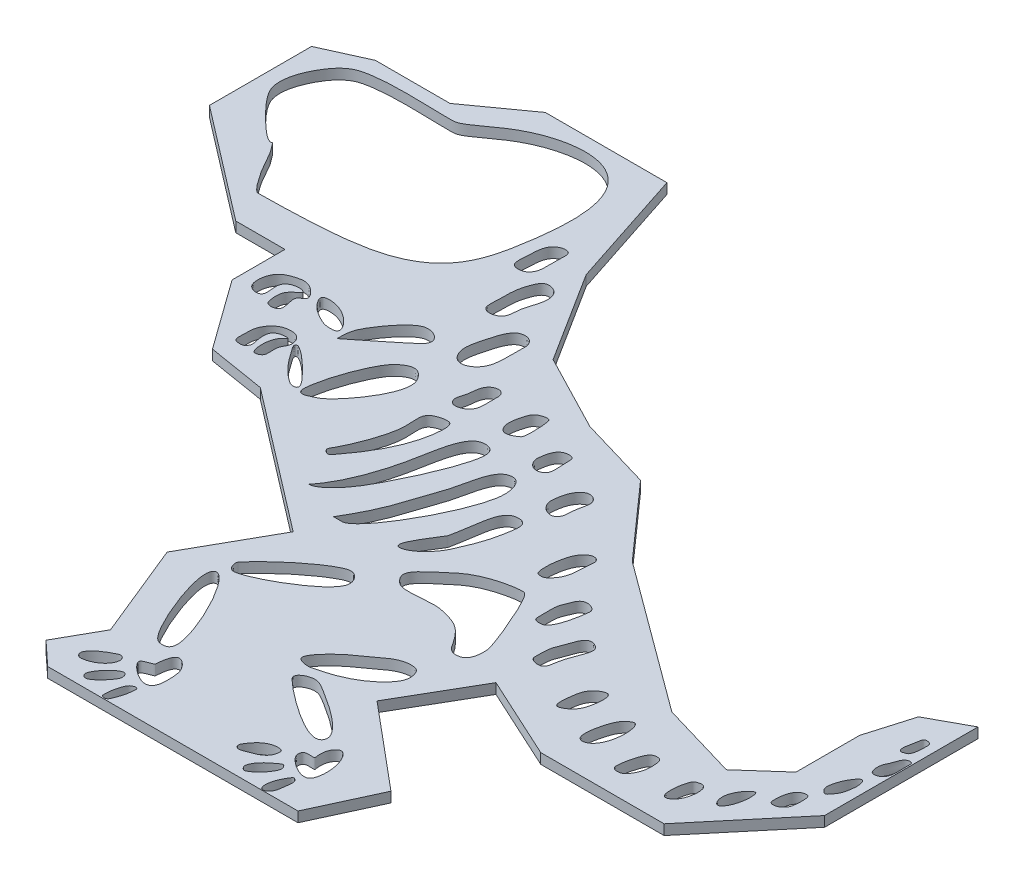
SolidWorks part; units mm, degrees
ref_plane "Front Plane" through (0, 0, 0) normal (0, 0, 1) x (1, 0, 0)
ref_plane "Top Plane" through (0, 0, 0) normal (0, 1, 0) x (1, 0, 0)
ref_plane "Right Plane" through (0, 0, 0) normal (1, 0, 0) x (0, 0, -1)
sketch "Sketch1" plane through (0, 0, 0) normal (0, 1, 0) x (1, 0, 0)
  line L0 (-169.545, -133.35) -> (169.545, 133.35) construction
  line L1 (-169.545, 133.35) -> (169.545, 133.35) construction
  line L2 (-169.545, 133.35) -> (-169.545, -133.35) construction
  line L3 (-169.545, -133.35) -> (169.545, -133.35)
  line L4 (169.545, 133.35) -> (169.545, -133.35)
  line L5 (-169.545, -133.35) -> (-174.8173, -133.35)
  line L6 (-174.8173, -133.35) -> (-174.8173, 138.6223)
  line L7 (-174.8173, 138.6223) -> (169.545, 138.6223)
  line L8 (169.545, 138.6223) -> (169.545, 133.35)
sketch "Sketch2" plane through (0, 0, 0) normal (0, 0, 1) x (1, 0, 0)
  line L0 (0, 0) -> (0, 8.058) construction
  line L1 (-169.545, 0) -> (169.545, 0) construction
sketch "Sketch3" plane through (0, 0, 0) normal (0, 1, 0) x (1, 0, 0)
  line L1 (-159.2597, 106.4446) -> (-159.6747, 106.0436)
  line L2 (-159.2597, 106.4446) -> (-159.6747, 106.0436)
  line L3 (-18.6637, -31.5909) -> (-15.6534, -31.5909)
  line L4 (-18.6637, -31.5909) -> (-15.6534, -31.5909)
  line L9 (-119.1442, 82.4182) -> (-126.9274, 73.6301)
  line L10 (-126.9274, 73.6301) -> (-137.0101, 81.885)
  line L11 (-137.0101, 81.885) -> (-141.0786, 71.6253)
  line L12 (-141.0786, 71.6253) -> (-148.2131, 74.2787)
  line L13 (-150.9255, 77.9344) -> (-138.2469, 90.3926)
  line L14 (-138.2469, 90.3926) -> (-128.1035, 81.885)
  line L15 (-128.1035, 81.885) -> (-119.8998, 89.6232)
  line L16 (-119.8998, 89.6232) -> (-109.2122, 83.2257)
  line L17 (-110.8894, 76.4014) -> (-119.1442, 82.4182)
  line L18 (-119.1442, 82.4182) -> (-126.9274, 73.6301)
  line L19 (-126.9274, 73.6301) -> (-137.0101, 81.885)
  line L20 (-137.0101, 81.885) -> (-141.0786, 71.6253)
  line L21 (-141.0786, 71.6253) -> (-148.2131, 74.2787)
  line L22 (-150.9255, 77.9344) -> (-138.2469, 90.3926)
  line L23 (-138.2469, 90.3926) -> (-128.1035, 81.885)
  line L24 (-128.1035, 81.885) -> (-119.8998, 89.6232)
  line L25 (-119.8998, 89.6232) -> (-109.2122, 83.2257)
  line L26 (-110.8894, 76.4014) -> (-119.1442, 82.4182)
  spline S1 degree 3 poles (-83.4964, 37.7764) (-91.1093, 38.0912) (-92.3245, 36.1465) (-89.8626, 33.2696) (-88.397, 31.9322) (-84.1735, 29.1669) (-80.5001, 28.5844) (-77.9719, 28.5767) (-77.5005, 31.3478) (-83.4964, 37.7764) (-91.1093, 38.0912) (-92.3245, 36.1465) knots -0.416074 -0.374123 -0.145741 0 0.019939 0.179451 0.222926 0.411215 0.451326 0.583926 0.625877 0.854259 1 1.019939 1.179451 1.222926 only from (-91.542, 37.3226) to (-91.542, 37.3226)
  spline S2 degree 3 poles (-83.4964, 37.7764) (-91.1093, 38.0912) (-92.3245, 36.1465) (-89.8626, 33.2696) (-88.397, 31.9322) (-84.1735, 29.1669) (-80.5001, 28.5844) (-77.9719, 28.5767) (-77.5005, 31.3478) (-83.4964, 37.7764) (-91.1093, 38.0912) (-92.3245, 36.1465) knots -0.416074 -0.374123 -0.145741 0 0.019939 0.179451 0.222926 0.411215 0.451326 0.583926 0.625877 0.854259 1 1.019939 1.179451 1.222926 only from (-91.542, 37.3226) to (-91.542, 37.3226)
  spline S3 degree 3 poles (-59.7777, 98.3682) (-63.3692, 98.4014) (-66.441, 95.0319) (-66.8153, 90.6073) (-67.2838, 84.4572) (-65.5283, 82.7312) (-60.9484, 82.8502) (-59.7732, 86.5836) (-59.8732, 90.2765) (-59.6775, 94.7624) (-59.7777, 98.3682) (-63.3692, 98.4014) (-66.441, 95.0319) knots -0.33571 -0.193808 -0.158463 0 0.042191 0.153707 0.286878 0.31643 0.449229 0.62682 0.66429 0.806192 0.841537 1 1.042191 1.153707 1.286878 only from (-64.4656, 97.0494) to (-64.4656, 97.0494)
  spline S4 degree 3 poles (-59.7777, 98.3682) (-63.3692, 98.4014) (-66.441, 95.0319) (-66.8153, 90.6073) (-67.2838, 84.4572) (-65.5283, 82.7312) (-60.9484, 82.8502) (-59.7732, 86.5836) (-59.8732, 90.2765) (-59.6775, 94.7624) (-59.7777, 98.3682) (-63.3692, 98.4014) (-66.441, 95.0319) knots -0.33571 -0.193808 -0.158463 0 0.042191 0.153707 0.286878 0.31643 0.449229 0.62682 0.66429 0.806192 0.841537 1 1.042191 1.153707 1.286878 only from (-64.4656, 97.0494) to (-64.4656, 97.0494)
  spline S5 degree 3 poles (14.2001, -33.8552) (10.7483, -36.7273) (17.6814, -43.0502) (26.9778, -40.4756) (36.8878, -42.7951) (39.9464, -44.1461) (45.1213, -50.7592) (46.4237, -54.2221) (52.7455, -52.611) (53.4487, -47.2061) (51.8775, -41.2033) (43.3886, -20.8685) (39.2427, -19.9873) (27.5948, -22.482) (14.2001, -33.8552) (10.7483, -36.7273) (17.6814, -43.0502) knots -0.34018 -0.233994 -0.198649 0 0.015838 0.142541 0.177932 0.33435 0.366263 0.465147 0.48407 0.536565 0.553469 0.636205 0.65982 0.766006 0.801351 1 1.015838 1.142541 1.177932 only from (14.503, -40.1234) to (14.503, -40.1234)
  spline S6 degree 3 poles (14.2001, -33.8552) (10.7483, -36.7273) (17.6814, -43.0502) (26.9778, -40.4756) (36.8878, -42.7951) (39.9464, -44.1461) (45.1213, -50.7592) (46.4237, -54.2221) (52.7455, -52.611) (53.4487, -47.2061) (51.8775, -41.2033) (43.3886, -20.8685) (39.2427, -19.9873) (27.5948, -22.482) (14.2001, -33.8552) (10.7483, -36.7273) (17.6814, -43.0502) knots -0.34018 -0.233994 -0.198649 0 0.015838 0.142541 0.177932 0.33435 0.366263 0.465147 0.48407 0.536565 0.553469 0.636205 0.65982 0.766006 0.801351 1 1.015838 1.142541 1.177932 only from (14.503, -40.1234) to (14.503, -40.1234)
  spline S7 degree 3 poles (26.0047, -74.9573) (19.169, -82.4247) (22.0563, -84.2759) (24.632, -84.9278) (29.7474, -83.5719) (39.1535, -81.1856) (48.2949, -71.7763) (47.2749, -67.058) (46.5636, -65.1254) (39.3339, -64.7282) (34.6947, -69.4264) (26.0047, -74.9573) (19.169, -82.4247) (22.0563, -84.2759) knots -0.403079 -0.256622 -0.214484 0 0.008451 0.076058 0.110192 0.341341 0.491167 0.514895 0.571534 0.596921 0.743378 0.785516 1 1.008451 1.076058 1.110192 only from (21.2279, -83.7304) to (21.2279, -83.7304)
  spline S8 degree 3 poles (26.0047, -74.9573) (19.169, -82.4247) (22.0563, -84.2759) (24.632, -84.9278) (29.7474, -83.5719) (39.1535, -81.1856) (48.2949, -71.7763) (47.2749, -67.058) (46.5636, -65.1254) (39.3339, -64.7282) (34.6947, -69.4264) (26.0047, -74.9573) (19.169, -82.4247) (22.0563, -84.2759) knots -0.403079 -0.256622 -0.214484 0 0.008451 0.076058 0.110192 0.341341 0.491167 0.514895 0.571534 0.596921 0.743378 0.785516 1 1.008451 1.076058 1.110192 only from (21.2279, -83.7304) to (21.2279, -83.7304)
  spline S9 degree 3 poles (-110.3256, 115.7371) (-118.5309, 110.1193) (-115.9035, 107.1299) (-109.9258, 107.4759) (-111.5274, 104.0614) (-109.8275, 101.823) (-103.0238, 105.7768) (-110.3256, 115.7371) (-118.5309, 110.1193) (-115.9035, 107.1299) knots -0.47372 -0.389255 -0.153946 0 0.145823 0.342645 0.49947 0.52628 0.610745 0.846054 1 1.145823 1.342645 1.49947 only from (-117.0248, 110.3881) to (-117.0248, 110.3881)
  spline S10 degree 3 poles (-110.3256, 115.7371) (-118.5309, 110.1193) (-115.9035, 107.1299) (-109.9258, 107.4759) (-111.5274, 104.0614) (-109.8275, 101.823) (-103.0238, 105.7768) (-110.3256, 115.7371) (-118.5309, 110.1193) (-115.9035, 107.1299) knots -0.47372 -0.389255 -0.153946 0 0.145823 0.342645 0.49947 0.52628 0.610745 0.846054 1 1.145823 1.342645 1.49947 only from (-117.0248, 110.3881) to (-117.0248, 110.3881)
  spline S11 degree 3 poles (1.2232, 31.4999) (0.7793, 27.8057) (0.2826, 24.0052) (2.5706, 20.2577) (6.9873, 21.5919) (7.6543, 25.3189) (7.2509, 29.9545) (7.1684, 32.1224) (5.3971, 32.6148) (1.2232, 31.4999) (0.7793, 27.8057) (0.2826, 24.0052) knots -0.379246 -0.286952 -0.247874 0 0.020185 0.201847 0.395049 0.435786 0.589947 0.620754 0.713048 0.752126 1 1.020185 1.201847 1.395049 only from (0.5283, 25.887) to (0.5283, 25.887)
  spline S12 degree 3 poles (1.2232, 31.4999) (0.7793, 27.8057) (0.2826, 24.0052) (2.5706, 20.2577) (6.9873, 21.5919) (7.6543, 25.3189) (7.2509, 29.9545) (7.1684, 32.1224) (5.3971, 32.6148) (1.2232, 31.4999) (0.7793, 27.8057) (0.2826, 24.0052) knots -0.379246 -0.286952 -0.247874 0 0.020185 0.201847 0.395049 0.435786 0.589947 0.620754 0.713048 0.752126 1 1.020185 1.201847 1.395049 only from (0.5283, 25.887) to (0.5283, 25.887)
  spline S13 degree 3 poles (-16.0328, 34.6718) (-16.763, 31.2747) (-14.4587, 25.8675) (-10.3993, 28.553) (-8.8009, 29.8175) (-8.9683, 38.3568) (-10.0899, 40.6949) (-14.394, 39.5126) (-16.0328, 34.6718) (-16.763, 31.2747) (-14.4587, 25.8675) knots -0.340573 -0.225318 -0.18982 0 0.042268 0.380415 0.444917 0.622786 0.659427 0.774682 0.81018 1 1.042268 1.380415 1.444917 only from (-16.1146, 29.9003) to (-16.1146, 29.9003)
  spline S14 degree 3 poles (4639.1562, 470.9456) (-802.5551, 1234.8923) (-156.2162, 59.4308) (-136.3734, 58.8784) (-112.761, 59.3323) (-91.3623, 61.468) (-75.678, 73.237) (-70.6131, 92.1296) (-68.2354, 123.5234) (-86.3806, 135.7876) (-107.5912, 131.2461) (-120.992, 119.0296) (-128.6914, 118.1657) (-148.4632, 119.9846) (-161.6319, 116.4474) (-167.4615, 108.6964) (-170.1367, 99.8112) (-167.6003, 91.2694) (-157.047, 81.1789) (-149.272, 75.5523) (-81.8694, 49.6716) (-2283.0752, 4597.4651) knots -0.288072 -0.288072 -0.288072 -0.288072 0.018984 0.022838 0.038537 0.169303 0.266188 0.380411 0.50257 0.526559 0.620305 0.67648 0.697256 0.813526 0.832888 0.876336 0.925656 0.937589 0.989212 0.996098 1.065895 1.065895 1.065895 1.065895 only from (-148.2131, 74.2787) to (-150.9255, 77.9344)
  spline S15 degree 3 poles (-2254.8838, 4589.8562) (-177.2639, -390.3034) (-94.8285, 119.6494) (-93.7764, 42.5095) (-186.4575, -71.2057) (-4592.7716, 2283.5264) knots -1.500368 -1.500368 -1.500368 -1.500368 0.274097 0.374097 4.949378 4.949378 4.949378 4.949378 only from (-109.2122, 83.2257) to (-110.8894, 76.4014)
  spline S16 degree 3 poles (-148.2131, 74.2787) (-143.4877, 65.3218) (-138.7147, 58.9436) (-136.3734, 58.8784) (-112.761, 59.3323) (-91.3623, 61.468) (-75.678, 73.237) (-70.6131, 92.1296) (-68.2354, 123.5234) (-86.3806, 135.7876) (-107.5912, 131.2461) (-120.992, 119.0296) (-128.6914, 118.1657) (-148.4632, 119.9846) (-161.6319, 116.4474) (-167.4615, 108.6964) (-170.1367, 99.8112) (-167.6003, 91.2694) (-157.047, 81.1789) (-153.265, 78.442) (-151.3692, 77.5232) (-150.9255, 77.9344) knots 0 0 0 0 0.018984 0.022838 0.038537 0.169303 0.266188 0.380411 0.50257 0.526559 0.620305 0.67648 0.697256 0.813526 0.832888 0.876336 0.925656 0.937589 0.989212 0.996098 1 1 1 1
  spline S17 degree 3 poles (-109.2122, 83.2257) (-97.916, 84.9745) (-94.5838, 101.7048) (-94.4206, 89.7447) (-96.5549, 79.6694) (-110.8894, 76.4014) knots 0 0 0 0 0.274097 0.374097 1 1 1 1
  spline S18 degree 3 poles (-16.0328, 34.6718) (-16.763, 31.2747) (-14.4587, 25.8675) (-10.3993, 28.553) (-8.8009, 29.8175) (-8.9683, 38.3568) (-10.0899, 40.6949) (-14.394, 39.5126) (-16.0328, 34.6718) (-16.763, 31.2747) (-14.4587, 25.8675) knots -0.340573 -0.225318 -0.18982 0 0.042268 0.380415 0.444917 0.622786 0.659427 0.774682 0.81018 1 1.042268 1.380415 1.444917 only from (-16.1146, 29.9003) to (-16.1146, 29.9003)
  spline S19 degree 3 poles (-48.7187, 30.6772) (-52.1964, 32.997) (-59.8929, 25.9145) (-65.3488, 11.1956) (-65.892, 1.1649) (-60.7021, 3.505) (-55.6996, 6.1213) (-43.7455, 22.5717) (-48.7187, 30.6772) (-52.1964, 32.997) (-59.8929, 25.9145) knots -0.711454 -0.234994 -0.157893 0 0.015508 0.139571 0.16247 0.221597 0.288546 0.765006 0.842107 1 1.015508 1.139571 1.16247 only from (-55.8971, 29.561) to (-55.8971, 29.561)
  spline S20 degree 3 poles (-48.7187, 30.6772) (-52.1964, 32.997) (-59.8929, 25.9145) (-65.3488, 11.1956) (-65.892, 1.1649) (-60.7021, 3.505) (-55.6996, 6.1213) (-43.7455, 22.5717) (-48.7187, 30.6772) (-52.1964, 32.997) (-59.8929, 25.9145) knots -0.711454 -0.234994 -0.157893 0 0.015508 0.139571 0.16247 0.221597 0.288546 0.765006 0.842107 1 1.015508 1.139571 1.16247 only from (-55.8971, 29.561) to (-55.8971, 29.561)
  spline S21 degree 3 poles (-5133.9575, -396.9891) (-205.5597, 69.9394) (-188.9531, 116.8601) (-145.5394, 103.6754) (-142.276, 108.3651) (-146.1216, 113.7541) (-202.2219, 105.4595) (128.9994, -34.2822) (-5148.5986, -164.5628) knots -2.980934 -2.980934 -2.980934 -2.980934 0.249242 0.292415 0.431727 0.617682 0.67451 3.961522 3.961522 3.961522 3.961522 only from (-159.6747, 106.0436) to (-159.2597, 106.4446)
  spline S22 degree 3 poles (-159.6747, 106.0436) (-154.5517, 105.9978) (-151.0315, 105.3434) (-145.5394, 103.6754) (-142.276, 108.3651) (-146.1216, 113.7541) (-155.1534, 112.4187) (-156.2051, 109.7963) (-159.2597, 106.4446) knots 0 0 0 0 0.249242 0.292415 0.431727 0.617682 0.67451 1 1 1 1
  spline S23 degree 3 poles (-94.3545, 127.2019) (-106.8747, 125.4021) (-102.5732, 114.6126) (-96.0125, 116.622) (-95.7894, 112.093) (-98.512, 108.507) (-98.1545, 104.575) (-92.0206, 103.476) (-81.5861, 107.858) (-78.4401, 116.3764) (-80.8545, 124.8838) (-85.4986, 127.9278) (-94.3545, 127.2019) (-106.8747, 125.4021) (-102.5732, 114.6126) knots -0.341594 -0.212181 -0.176404 0 0.00701 0.06309 0.075821 0.127314 0.164214 0.194635 0.431528 0.62116 0.658406 0.787819 0.823596 1 1.00701 1.06309 1.075821 only from (-103.8121, 117.7608) to (-103.8121, 117.7608)
  spline S24 degree 3 poles (-94.3545, 127.2019) (-106.8747, 125.4021) (-102.5732, 114.6126) (-96.0125, 116.622) (-95.7894, 112.093) (-98.512, 108.507) (-98.1545, 104.575) (-92.0206, 103.476) (-81.5861, 107.858) (-78.4401, 116.3764) (-80.8545, 124.8838) (-85.4986, 127.9278) (-94.3545, 127.2019) (-106.8747, 125.4021) (-102.5732, 114.6126) knots -0.341594 -0.212181 -0.176404 0 0.00701 0.06309 0.075821 0.127314 0.164214 0.194635 0.431528 0.62116 0.658406 0.787819 0.823596 1 1.00701 1.06309 1.075821 only from (-103.8121, 117.7608) to (-103.8121, 117.7608)
  spline S25 degree 3 poles (53.5634, -113.0402) (51.2421, -112.7967) (51.5228, -117.2525) (58.1989, -121.9472) (62.2943, -120.4276) (63.5727, -111.4641) (59.4982, -104.5919) (55.3217, -107.738) (55.597, -112.8592) (55.9074, -113.1102) (53.5634, -113.0402) (51.2421, -112.7967) (51.5228, -117.2525) knots -0.329975 -0.186168 -0.153171 0 0.017019 0.153169 0.178135 0.249653 0.420162 0.462199 0.670025 0.813832 0.846829 1 1.017019 1.153169 1.178135 only from (51.3879, -114.8039) to (51.3879, -114.8039)
  spline S26 degree 3 poles (53.5634, -113.0402) (51.2421, -112.7967) (51.5228, -117.2525) (58.1989, -121.9472) (62.2943, -120.4276) (63.5727, -111.4641) (59.4982, -104.5919) (55.3217, -107.738) (55.597, -112.8592) (55.9074, -113.1102) (53.5634, -113.0402) (51.2421, -112.7967) (51.5228, -117.2525) knots -0.329975 -0.186168 -0.153171 0 0.017019 0.153169 0.178135 0.249653 0.420162 0.462199 0.670025 0.813832 0.846829 1 1.017019 1.153169 1.178135 only from (51.3879, -114.8039) to (51.3879, -114.8039)
  spline S27 degree 3 poles (116.0178, -50.43) (114.1056, -58.7942) (115.2767, -61.2373) (118.3813, -61.1373) (121.4212, -56.5786) (121.7433, -53.5342) (121.0677, -48.7928) (118.7536, -48.5883) (116.0178, -50.43) (114.1056, -58.7942) (115.2767, -61.2373) knots -0.349445 -0.211705 -0.175039 0 0.017058 0.153519 0.216852 0.587061 0.650555 0.788295 0.824961 1 1.017058 1.153519 1.216852 only from (114.6868, -59.9248) to (114.6868, -59.9248)
  spline S28 degree 3 poles (116.0178, -50.43) (114.1056, -58.7942) (115.2767, -61.2373) (118.3813, -61.1373) (121.4212, -56.5786) (121.7433, -53.5342) (121.0677, -48.7928) (118.7536, -48.5883) (116.0178, -50.43) (114.1056, -58.7942) (115.2767, -61.2373) knots -0.349445 -0.211705 -0.175039 0 0.017058 0.153519 0.216852 0.587061 0.650555 0.788295 0.824961 1 1.017058 1.153519 1.216852 only from (114.6868, -59.9248) to (114.6868, -59.9248)
  spline S29 degree 3 poles (-3.3226, -125.4508) (-4.3848, -130.4052) (-3.9955, -132.8379) (-2.0749, -133.3116) (-0.4685, -129.38) (0.1791, -127.1568) (0.3863, -123.038) (-1.777, -123.942) (-3.3226, -125.4508) (-4.3848, -130.4052) (-3.9955, -132.8379) knots -0.631672 -0.517972 -0.453384 0 0.009256 0.083305 0.118716 0.32796 0.368328 0.482028 0.546616 1 1.009256 1.083305 1.118716 only from (-4.0621, -132.4174) to (-4.0621, -132.4174)
  spline S30 degree 3 poles (-3.3226, -125.4508) (-4.3848, -130.4052) (-3.9955, -132.8379) (-2.0749, -133.3116) (-0.4685, -129.38) (0.1791, -127.1568) (0.3863, -123.038) (-1.777, -123.942) (-3.3226, -125.4508) (-4.3848, -130.4052) (-3.9955, -132.8379) knots -0.631672 -0.517972 -0.453384 0 0.009256 0.083305 0.118716 0.32796 0.368328 0.482028 0.546616 1 1.009256 1.083305 1.118716 only from (-4.0621, -132.4174) to (-4.0621, -132.4174)
  spline S31 degree 3 poles (37.0435, -1.0873) (36.5203, -11.6869) (39.2858, -12.1707) (40.5554, -12.3267) (44.8329, -6.8035) (44.3083, -2.3906) (45.2002, 4.1209) (41.9006, 4.8346) (37.0435, -1.0873) (36.5203, -11.6869) (39.2858, -12.1707) knots -0.440773 -0.268321 -0.222088 0 0.02078 0.187024 0.240791 0.504684 0.559227 0.731679 0.777912 1 1.02078 1.187024 1.240791 only from (37.8964, -11.8619) to (37.8964, -11.8619)
  spline S32 degree 3 poles (37.0435, -1.0873) (36.5203, -11.6869) (39.2858, -12.1707) (40.5554, -12.3267) (44.8329, -6.8035) (44.3083, -2.3906) (45.2002, 4.1209) (41.9006, 4.8346) (37.0435, -1.0873) (36.5203, -11.6869) (39.2858, -12.1707) knots -0.440773 -0.268321 -0.222088 0 0.02078 0.187024 0.240791 0.504684 0.559227 0.731679 0.777912 1 1.02078 1.187024 1.240791 only from (37.8964, -11.8619) to (37.8964, -11.8619)
  spline S33 degree 3 poles (166.2735, 6.6872) (163.446, 7.0482) (162.9479, 3.2565) (161.889, 0.2794) (162.84, -1.9561) (163.8152, -1.4988) (166.092, -0.927) (166.2921, 3.1544) (166.2735, 6.6872) (163.446, 7.0482) (162.9479, 3.2565) knots -0.426404 -0.142769 -0.096583 0 0.033267 0.299406 0.35322 0.517595 0.573596 0.857231 0.903417 1 1.033267 1.299406 1.35322 only from (163.4925, 6.3429) to (163.4925, 6.3429)
  spline S34 degree 3 poles (166.2735, 6.6872) (163.446, 7.0482) (162.9479, 3.2565) (161.889, 0.2794) (162.84, -1.9561) (163.8152, -1.4988) (166.092, -0.927) (166.2921, 3.1544) (166.2735, 6.6872) (163.446, 7.0482) (162.9479, 3.2565) knots -0.426404 -0.142769 -0.096583 0 0.033267 0.299406 0.35322 0.517595 0.573596 0.857231 0.903417 1 1.033267 1.299406 1.35322 only from (163.4925, 6.3429) to (163.4925, 6.3429)
  spline S35 degree 3 poles (150.476, -47.4606) (149.6189, -41.7857) (147.4866, -42.1546) (143.0824, -48.2683) (146.6877, -56.0409) (150.476, -47.4606) (149.6189, -41.7857) (147.4866, -42.1546) knots -0.641609 -0.481952 -0.111593 0 0.035839 0.358391 0.518048 0.888407 1 1.035839 1.358391 1.518048 only from (149.2501, -41.9475) to (149.2501, -41.9475)
  spline S36 degree 3 poles (150.476, -47.4606) (149.6189, -41.7857) (147.4866, -42.1546) (143.0824, -48.2683) (146.6877, -56.0409) (150.476, -47.4606) (149.6189, -41.7857) (147.4866, -42.1546) knots -0.641609 -0.481952 -0.111593 0 0.035839 0.358391 0.518048 0.888407 1 1.035839 1.358391 1.518048 only from (149.2501, -41.9475) to (149.2501, -41.9475)
  spline S37 degree 3 poles (-67.0618, 5.7709) (-76.4091, 14.9391) (-80.9309, 17.2368) (-81.942, 16.6977) (-75.8142, 7.7036) (-72.5906, 5.3163) (-69.3851, 3.0079) (-67.1516, 2.9909) (-67.0618, 5.7709) (-76.4091, 14.9391) (-80.9309, 17.2368) knots -0.317691 -0.218329 -0.185318 0 0.004766 0.042894 0.109883 0.607666 0.682309 0.781671 0.814682 1 1.004766 1.042894 1.109883 only from (-79.9839, 16.7532) to (-79.9839, 16.7532)
  spline S38 degree 3 poles (-67.0618, 5.7709) (-76.4091, 14.9391) (-80.9309, 17.2368) (-81.942, 16.6977) (-75.8142, 7.7036) (-72.5906, 5.3163) (-69.3851, 3.0079) (-67.1516, 2.9909) (-67.0618, 5.7709) (-76.4091, 14.9391) (-80.9309, 17.2368) knots -0.317691 -0.218329 -0.185318 0 0.004766 0.042894 0.109883 0.607666 0.682309 0.781671 0.814682 1 1.004766 1.042894 1.109883 only from (-79.9839, 16.7532) to (-79.9839, 16.7532)
  spline S39 degree 3 poles (17.7444, 21.4282) (16.9206, 16.9256) (16.4497, 10.9496) (21.4059, 8.1953) (24.735, 12.3152) (23.3618, 12.7837) (25.6587, 22.1288) (22.1601, 24.1275) (17.7444, 21.4282) (16.9206, 16.9256) (16.4497, 10.9496) knots -0.286359 -0.200897 -0.171193 0 0.035053 0.315479 0.385774 0.667715 0.713641 0.799103 0.828807 1 1.035053 1.315479 1.385774 only from (16.8039, 15.2944) to (16.8039, 15.2944)
  spline S40 degree 3 poles (17.7444, 21.4282) (16.9206, 16.9256) (16.4497, 10.9496) (21.4059, 8.1953) (24.735, 12.3152) (23.3618, 12.7837) (25.6587, 22.1288) (22.1601, 24.1275) (17.7444, 21.4282) (16.9206, 16.9256) (16.4497, 10.9496) knots -0.286359 -0.200897 -0.171193 0 0.035053 0.315479 0.385774 0.667715 0.713641 0.799103 0.828807 1 1.035053 1.315479 1.385774 only from (16.8039, 15.2944) to (16.8039, 15.2944)
  spline S41 degree 3 poles (-25.4195, -15.9269) (-33.6031, -25.4822) (-33.9723, -25.6936) (-30.7487, -26.1088) (-20.7778, -13.1791) (-9.2036, 12.1292) (-10.7058, 20.0645) (-17.5095, 21.0923) (-20.5334, 13.2032) (-25.4195, -15.9269) (-33.6031, -25.4822) (-33.9723, -25.6936) knots -0.424615 -0.331589 -0.289127 0 0.029367 0.264302 0.315128 0.486805 0.514977 0.575385 0.668411 0.710873 1 1.029367 1.264302 1.315128 only from (-33.7168, -25.5108) to (-33.7168, -25.5108)
  spline S42 degree 3 poles (-25.4195, -15.9269) (-33.6031, -25.4822) (-33.9723, -25.6936) (-30.7487, -26.1088) (-20.7778, -13.1791) (-9.2036, 12.1292) (-10.7058, 20.0645) (-17.5095, 21.0923) (-20.5334, 13.2032) (-25.4195, -15.9269) (-33.6031, -25.4822) (-33.9723, -25.6936) knots -0.424615 -0.331589 -0.289127 0 0.029367 0.264302 0.315128 0.486805 0.514977 0.575385 0.668411 0.710873 1 1.029367 1.264302 1.315128 only from (-33.7168, -25.5108) to (-33.7168, -25.5108)
  spline S43 degree 3 poles (-75.825, 30.4671) (-75.4833, 26.7648) (-76.1791, 26.1328) (-64.5255, 35.5021) (-54.6935, 43.4703) (-60.027, 47.3693) (-66.6386, 45.951) (-73.4093, 36.3888) (-75.825, 30.4671) (-75.4833, 26.7648) (-76.1791, 26.1328) knots -0.366772 -0.182134 -0.143149 0 0.035009 0.350086 0.465041 0.595637 0.633228 0.817866 0.856851 1 1.035009 1.350086 1.465041 only from (-75.6564, 26.7347) to (-75.6564, 26.7347)
  spline S44 degree 3 poles (-75.825, 30.4671) (-75.4833, 26.7648) (-76.1791, 26.1328) (-64.5255, 35.5021) (-54.6935, 43.4703) (-60.027, 47.3693) (-66.6386, 45.951) (-73.4093, 36.3888) (-75.825, 30.4671) (-75.4833, 26.7648) (-76.1791, 26.1328) knots -0.366772 -0.182134 -0.143149 0 0.035009 0.350086 0.465041 0.595637 0.633228 0.817866 0.856851 1 1.035009 1.350086 1.465041 only from (-75.6564, 26.7347) to (-75.6564, 26.7347)
  spline S45 degree 3 poles (154.9833, -40.1852) (155.2078, -43.1713) (157.8214, -42.8592) (159.9962, -40.7546) (160.6569, -40.1318) (160.6628, -34.751) (160.5438, -33.2199) (154.9116, -32.7336) (154.9833, -40.1852) (155.2078, -43.1713) (157.8214, -42.8592) knots -0.330701 -0.330701 0 0 0.323079 0.323079 0.615276 0.615276 0.669299 0.669299 1 1 1.323079 1.323079 1.615276 only from (155.0968, -41.6956) to (155.0968, -41.6956)
  spline S46 degree 3 poles (154.9833, -40.1852) (155.2078, -43.1713) (157.8214, -42.8592) (159.9962, -40.7546) (160.6569, -40.1318) (160.6628, -34.751) (160.5438, -33.2199) (154.9116, -32.7336) (154.9833, -40.1852) (155.2078, -43.1713) (157.8214, -42.8592) knots -0.330701 -0.330701 0 0 0.323079 0.323079 0.615276 0.615276 0.669299 0.669299 1 1 1.323079 1.323079 1.615276 only from (155.0968, -41.6956) to (155.0968, -41.6956)
  spline S47 degree 3 poles (133.0015, -50.5651) (131.5435, -61.333) (138.1694, -59.2019) (139.0313, -51.6054) (137.224, -49.0915) (135.5309, -49.3555) (133.0015, -50.5651) (131.5435, -61.333) (138.1694, -59.2019) knots -0.525379 -0.323564 -0.268503 0 0.044939 0.404455 0.474621 0.676436 0.731497 1 1.044939 1.404455 1.474621 only from (133.8336, -60.4163) to (133.8336, -60.4163)
  spline S48 degree 3 poles (133.0015, -50.5651) (131.5435, -61.333) (138.1694, -59.2019) (139.0313, -51.6054) (137.224, -49.0915) (135.5309, -49.3555) (133.0015, -50.5651) (131.5435, -61.333) (138.1694, -59.2019) knots -0.525379 -0.323564 -0.268503 0 0.044939 0.404455 0.474621 0.676436 0.731497 1 1.044939 1.404455 1.474621 only from (133.8336, -60.4163) to (133.8336, -60.4163)
  spline S49 degree 3 poles (-54.5503, 84.6129) (-56.8248, 80.1217) (-58.1944, 75.7993) (-58.0288, 68.4745) (-58.9869, 62.5105) (-50.5505, 63.678) (-51.4509, 70.7409) (-48.8093, 75.8466) (-48.9572, 82.4788) (-54.5503, 84.6129) (-56.8248, 80.1217) (-58.1944, 75.7993) knots -0.339136 -0.306748 -0.146065 0 0.196712 0.227714 0.310019 0.41906 0.530055 0.660864 0.693252 0.853935 1 1.196712 1.227714 1.310019 only from (-56.5429, 80.409) to (-56.5429, 80.409)
  spline S50 degree 3 poles (-54.5503, 84.6129) (-56.8248, 80.1217) (-58.1944, 75.7993) (-58.0288, 68.4745) (-58.9869, 62.5105) (-50.5505, 63.678) (-51.4509, 70.7409) (-48.8093, 75.8466) (-48.9572, 82.4788) (-54.5503, 84.6129) (-56.8248, 80.1217) (-58.1944, 75.7993) knots -0.339136 -0.306748 -0.146065 0 0.196712 0.227714 0.310019 0.41906 0.530055 0.660864 0.693252 0.853935 1 1.196712 1.227714 1.310019 only from (-56.5429, 80.409) to (-56.5429, 80.409)
  spline S51 degree 3 poles (-48.4575, 50.7091) (-49.2626, 47.1681) (-46.7978, 41.3117) (-43.0237, 41.3188) (-37.4146, 46.0126) (-38.0073, 51.1059) (-37.4862, 62.9135) (-43.2815, 63.5345) (-46.324, 58.818) (-47.0643, 56.0375) (-48.4575, 50.7091) (-49.2626, 47.1681) (-46.7978, 41.3117) knots -0.238976 -0.120095 -0.094711 0 0.018863 0.169766 0.224468 0.511187 0.56694 0.72625 0.761024 0.879905 0.905289 1 1.018863 1.169766 1.224468 only from (-48.5084, 45.499) to (-48.5084, 45.499)
  spline S52 degree 3 poles (-48.4575, 50.7091) (-49.2626, 47.1681) (-46.7978, 41.3117) (-43.0237, 41.3188) (-37.4146, 46.0126) (-38.0073, 51.1059) (-37.4862, 62.9135) (-43.2815, 63.5345) (-46.324, 58.818) (-47.0643, 56.0375) (-48.4575, 50.7091) (-49.2626, 47.1681) (-46.7978, 41.3117) knots -0.238976 -0.120095 -0.094711 0 0.018863 0.169766 0.224468 0.511187 0.56694 0.72625 0.761024 0.879905 0.905289 1 1.018863 1.169766 1.224468 only from (-48.5084, 45.499) to (-48.5084, 45.499)
  spline S53 degree 3 poles (99.4226, -46.306) (96.777, -59.0302) (102.5601, -57.362) (106.7955, -51.0094) (106.0389, -40.492) (101.4375, -43.4666) (99.4226, -46.306) (96.777, -59.0302) (102.5601, -57.362) knots -0.542833 -0.482936 -0.2732 0 0.115049 0.164425 0.457167 0.517064 0.7268 1 1.115049 1.164425 1.457167 only from (99.4683, -57.5719) to (99.4683, -57.5719)
  spline S54 degree 3 poles (99.4226, -46.306) (96.777, -59.0302) (102.5601, -57.362) (106.7955, -51.0094) (106.0389, -40.492) (101.4375, -43.4666) (99.4226, -46.306) (96.777, -59.0302) (102.5601, -57.362) knots -0.542833 -0.482936 -0.2732 0 0.115049 0.164425 0.457167 0.517064 0.7268 1 1.115049 1.164425 1.457167 only from (99.4683, -57.5719) to (99.4683, -57.5719)
  spline S55 degree 3 poles (163.3984, -10.171) (163.7975, -13.4123) (165.9075, -14.4891) (168.2103, -13.268) (169.3048, -9.9441) (168.9278, -6.4947) (169.0667, -2.7932) (165.8653, -3.1153) (165.3231, -6.6557) (163.3984, -10.171) (163.7975, -13.4123) (165.9075, -14.4891) knots -0.29957 -0.180218 -0.150261 0 0.025273 0.227458 0.285534 0.547964 0.592733 0.70043 0.819782 0.849739 1 1.025273 1.227458 1.285534 only from (164.509, -13.7216) to (164.509, -13.7216)
  spline S56 degree 3 poles (163.3984, -10.171) (163.7975, -13.4123) (165.9075, -14.4891) (168.2103, -13.268) (169.3048, -9.9441) (168.9278, -6.4947) (169.0667, -2.7932) (165.8653, -3.1153) (165.3231, -6.6557) (163.3984, -10.171) (163.7975, -13.4123) (165.9075, -14.4891) knots -0.29957 -0.180218 -0.150261 0 0.025273 0.227458 0.285534 0.547964 0.592733 0.70043 0.819782 0.849739 1 1.025273 1.227458 1.285534 only from (164.509, -13.7216) to (164.509, -13.7216)
  spline S57 degree 3 poles (161.3605, -21.8397) (160.4265, -26.1132) (160.9032, -28.4264) (162.615, -30.0315) (164.4985, -27.3078) (165.6961, -26.4673) (166.3158, -20.261) (165.3082, -16.535) (161.3605, -21.8397) (160.4265, -26.1132) (160.9032, -28.4264) knots -0.398326 -0.304359 -0.196628 0 0.019319 0.173869 0.232992 0.551428 0.601674 0.695641 0.803372 1 1.019319 1.173869 1.232992 only from (160.6619, -27.2082) to (160.6619, -27.2082)
  spline S58 degree 3 poles (161.3605, -21.8397) (160.4265, -26.1132) (160.9032, -28.4264) (162.615, -30.0315) (164.4985, -27.3078) (165.6961, -26.4673) (166.3158, -20.261) (165.3082, -16.535) (161.3605, -21.8397) (160.4265, -26.1132) (160.9032, -28.4264) knots -0.398326 -0.304359 -0.196628 0 0.019319 0.173869 0.232992 0.551428 0.601674 0.695641 0.803372 1 1.019319 1.173869 1.232992 only from (160.6619, -27.2082) to (160.6619, -27.2082)
  spline S59 degree 3 poles (-7.5298, -92.0241) (-21.2382, -66.6138) (-25.9456, -76.7543) (-14.8244, -103.3442) (-9.3854, -105.1667) (-6.1821, -104.8261) (-7.5298, -92.0241) (-21.2382, -66.6138) (-25.9456, -76.7543) knots -0.584036 -0.45219 -0.392138 0 0.039948 0.359535 0.415964 0.54781 0.607862 1 1.039948 1.359535 1.415964 only from (-23.3641, -71.6056) to (-23.3641, -71.6056)
  spline S60 degree 3 poles (-7.5298, -92.0241) (-21.2382, -66.6138) (-25.9456, -76.7543) (-14.8244, -103.3442) (-9.3854, -105.1667) (-6.1821, -104.8261) (-7.5298, -92.0241) (-21.2382, -66.6138) (-25.9456, -76.7543) knots -0.584036 -0.45219 -0.392138 0 0.039948 0.359535 0.415964 0.54781 0.607862 1 1.039948 1.359535 1.415964 only from (-23.3641, -71.6056) to (-23.3641, -71.6056)
  spline S61 degree 3 poles (65.1045, -32.7518) (64.0841, -32.9361) (64.188, -40.885) (69.5032, -42.1727) (69.7482, -38.2) (71.0728, -31.8058) (73.6629, -27.5361) (72.5287, -24.6123) (68.03, -22.4386) (65.1045, -32.7518) (64.0841, -32.9361) (64.188, -40.885) knots -0.618451 -0.526367 -0.321115 0 0.007401 0.074012 0.145377 0.175108 0.349517 0.381549 0.473633 0.678885 1 1.007401 1.074012 1.145377 only from (64.1669, -39.2505) to (64.1669, -39.2505)
  spline S62 degree 3 poles (65.1045, -32.7518) (64.0841, -32.9361) (64.188, -40.885) (69.5032, -42.1727) (69.7482, -38.2) (71.0728, -31.8058) (73.6629, -27.5361) (72.5287, -24.6123) (68.03, -22.4386) (65.1045, -32.7518) (64.0841, -32.9361) (64.188, -40.885) knots -0.618451 -0.526367 -0.321115 0 0.007401 0.074012 0.145377 0.175108 0.349517 0.381549 0.473633 0.678885 1 1.007401 1.074012 1.145377 only from (64.1669, -39.2505) to (64.1669, -39.2505)
  spline S63 degree 3 poles (84.5325, -39.6929) (83.7818, -44.1164) (83.0955, -52.0648) (88.7583, -49.4103) (90.7523, -45.2985) (91.1959, -36.2823) (84.5325, -39.6929) (83.7818, -44.1164) (83.0955, -52.0648) knots -0.532893 -0.349963 -0.256566 0 0.149525 0.215411 0.467107 0.650037 0.743434 1 1.149525 1.215411 1.467107 only from (83.6288, -46.3586) to (83.6288, -46.3586)
  spline S64 degree 3 poles (84.5325, -39.6929) (83.7818, -44.1164) (83.0955, -52.0648) (88.7583, -49.4103) (90.7523, -45.2985) (91.1959, -36.2823) (84.5325, -39.6929) (83.7818, -44.1164) (83.0955, -52.0648) knots -0.532893 -0.349963 -0.256566 0 0.149525 0.215411 0.467107 0.650037 0.743434 1 1.149525 1.215411 1.467107 only from (83.6288, -46.3586) to (83.6288, -46.3586)
  spline S65 degree 3 poles (30.012, -86.5198) (23.9065, -89.7847) (30.5529, -96.2273) (48.4864, -109.3804) (54.7253, -102.0458) (39.5391, -91.9832) (30.012, -86.5198) (23.9065, -89.7847) (30.5529, -96.2273) knots -0.565541 -0.186609 -0.125318 0 0.038709 0.348384 0.434459 0.813391 0.874682 1 1.038709 1.348384 1.434459 only from (25.4974, -90.9545) to (25.4974, -90.9545)
  spline S66 degree 3 poles (30.012, -86.5198) (23.9065, -89.7847) (30.5529, -96.2273) (48.4864, -109.3804) (54.7253, -102.0458) (39.5391, -91.9832) (30.012, -86.5198) (23.9065, -89.7847) (30.5529, -96.2273) knots -0.565541 -0.186609 -0.125318 0 0.038709 0.348384 0.434459 0.813391 0.874682 1 1.038709 1.348384 1.434459 only from (25.4974, -90.9545) to (25.4974, -90.9545)
  spline S67 degree 3 poles (9.9775, -13.3304) (0.6836, -30.2048) (7.8703, -28.1108) (12.4686, -23.1134) (16.6292, -13.4903) (18.1767, -9.4193) (19.9409, 2.5233) (15.1984, 2.6829) (10.7579, -0.1086) (10.6453, -7.4221) (8.2581, -18.6449) (9.9775, -13.3304) (0.6836, -30.2048) (7.8703, -28.1108) knots -0.35119 -0.294031 -0.07693 0 0.008075 0.072675 0.09935 0.248152 0.275226 0.343009 0.384518 0.64881 0.705969 0.92307 1 1.008075 1.072675 1.09935 only from (4.0517, -29.1874) to (4.0517, -29.1874)
  spline S68 degree 3 poles (9.9775, -13.3304) (0.6836, -30.2048) (7.8703, -28.1108) (12.4686, -23.1134) (16.6292, -13.4903) (18.1767, -9.4193) (19.9409, 2.5233) (15.1984, 2.6829) (10.7579, -0.1086) (10.6453, -7.4221) (8.2581, -18.6449) (9.9775, -13.3304) (0.6836, -30.2048) (7.8703, -28.1108) knots -0.35119 -0.294031 -0.07693 0 0.008075 0.072675 0.09935 0.248152 0.275226 0.343009 0.384518 0.64881 0.705969 0.92307 1 1.008075 1.072675 1.09935 only from (4.0517, -29.1874) to (4.0517, -29.1874)
  spline S69 degree 3 poles (2141.4856, 4477.0646) (-373.2046, -507.9527) (8.7211, -42.7734) (5.8509, 11.6015) (3.7284, 15.0576) (-3.805, 14.0411) (-4.489, 2.729) (-34.1044, -76.3421) (114.5904, 215.7551) (-2627.9563, -4296.5149) knots -1.083654 -1.083654 -1.083654 -1.083654 0.255506 0.293205 0.367675 0.400617 0.589687 0.651989 2.799812 2.799812 2.799812 2.799812 only from (-15.6534, -31.5909) to (-18.6637, -31.5909)
  spline S70 degree 3 poles (-15.6534, -31.5909) (-10.2854, -31.9146) (6.578, -2.1736) (5.8509, 11.6015) (3.7284, 15.0576) (-3.805, 14.0411) (-4.489, 2.729) (-11.8877, -17.0251) (-10.8873, -17.9698) (-18.6637, -31.5909) knots 0 0 0 0 0.255506 0.293205 0.367675 0.400617 0.589687 0.651989 1 1 1 1
  spline S71 degree 3 poles (-8.7035, -120.2502) (-14.2333, -126.0878) (-14.4025, -129.5655) (-12.9158, -130.3612) (-9.8566, -128.7111) (-6.5461, -124.73) (-6.1158, -122.7955) (-6.403, -121.3879) (-8.7035, -120.2502) (-14.2333, -126.0878) (-14.4025, -129.5655) knots -0.472168 -0.356831 -0.308172 0 0.015962 0.143654 0.194996 0.478035 0.527832 0.643169 0.691828 1 1.015962 1.143654 1.194996 only from (-14.3314, -128.3307) to (-14.3314, -128.3307)
  spline S72 degree 3 poles (-8.7035, -120.2502) (-14.2333, -126.0878) (-14.4025, -129.5655) (-12.9158, -130.3612) (-9.8566, -128.7111) (-6.5461, -124.73) (-6.1158, -122.7955) (-6.403, -121.3879) (-8.7035, -120.2502) (-14.2333, -126.0878) (-14.4025, -129.5655) knots -0.472168 -0.356831 -0.308172 0 0.015962 0.143654 0.194996 0.478035 0.527832 0.643169 0.691828 1 1.015962 1.143654 1.194996 only from (-14.3314, -128.3307) to (-14.3314, -128.3307)
  spline S73 degree 3 poles (-96.158, 32.878) (-92.0135, 33.7446) (-97.9716, 39.8898) (-105.0453, 38.2561) (-109.2626, 36.3399) (-110.0142, 26.5608) (-102.1971, 25.9329) (-105.2392, 33.8289) (-101.4084, 35.9473) (-98.0385, 36.0436) (-96.7658, 35.4294) (-97.2232, 34.5258) (-101.0919, 32.4119) (-100.8791, 28.05) (-100.0765, 24.3886) (-93.7826, 24.7558) (-96.8734, 29.7814) (-96.158, 32.878) (-92.0135, 33.7446) (-97.9716, 39.8898) knots -0.18438 -0.067535 -0.049097 0 0.094857 0.116602 0.217456 0.292257 0.349906 0.420598 0.490923 0.502433 0.531999 0.545686 0.635614 0.729475 0.747476 0.81562 0.932465 0.950903 1 1.094857 1.116602 1.217456 only from (-94.2108, 34.0321) to (-94.2108, 34.0321)
  spline S74 degree 3 poles (-96.158, 32.878) (-92.0135, 33.7446) (-97.9716, 39.8898) (-105.0453, 38.2561) (-109.2626, 36.3399) (-110.0142, 26.5608) (-102.1971, 25.9329) (-105.2392, 33.8289) (-101.4084, 35.9473) (-98.0385, 36.0436) (-96.7658, 35.4294) (-97.2232, 34.5258) (-101.0919, 32.4119) (-100.8791, 28.05) (-100.0765, 24.3886) (-93.7826, 24.7558) (-96.8734, 29.7814) (-96.158, 32.878) (-92.0135, 33.7446) (-97.9716, 39.8898) knots -0.18438 -0.067535 -0.049097 0 0.094857 0.116602 0.217456 0.292257 0.349906 0.420598 0.490923 0.502433 0.531999 0.545686 0.635614 0.729475 0.747476 0.81562 0.932465 0.950903 1 1.094857 1.116602 1.217456 only from (-94.2108, 34.0321) to (-94.2108, 34.0321)
  spline S75 degree 3 poles (-28.375, 21.0946) (-31.8286, 20.175) (-36.0496, 17.5736) (-32.1411, 11.1244) (-39.5877, -7.1075) (-42.3876, -11.2756) (-39.7935, -12.904) (-37.6866, -9.8712) (-27.515, 2.8326) (-25.8026, 19.5361) (-28.375, 21.0946) (-31.8286, 20.175) (-36.0496, 17.5736) knots -0.186231 -0.089391 -0.070768 0 0.025582 0.255816 0.500363 0.535 0.594718 0.623341 0.813769 0.910609 0.929232 1 1.025582 1.255816 1.500363 only from (-32.2964, 19.8153) to (-32.2964, 19.8153)
  spline S76 degree 3 poles (-28.375, 21.0946) (-31.8286, 20.175) (-36.0496, 17.5736) (-32.1411, 11.1244) (-39.5877, -7.1075) (-42.3876, -11.2756) (-39.7935, -12.904) (-37.6866, -9.8712) (-27.515, 2.8326) (-25.8026, 19.5361) (-28.375, 21.0946) (-31.8286, 20.175) (-36.0496, 17.5736) knots -0.186231 -0.089391 -0.070768 0 0.025582 0.255816 0.500363 0.535 0.594718 0.623341 0.813769 0.910609 0.929232 1 1.025582 1.255816 1.500363 only from (-32.2964, 19.8153) to (-32.2964, 19.8153)
  spline S77 degree 3 poles (-33.3619, 31.919) (-34.6647, 30.1321) (-33.1015, 25.7855) (-26.3355, 27.8983) (-26.8287, 34.6853) (-26.2977, 41.0424) (-32.1064, 40.4465) (-33.133, 36.1039) (-33.3619, 31.919) (-34.6647, 30.1321) (-33.1015, 25.7855) knots -0.299754 -0.166898 -0.136922 0 0.023978 0.239776 0.366941 0.500447 0.700246 0.833102 0.863078 1 1.023978 1.239776 1.366941 only from (-34.1568, 28.8211) to (-34.1568, 28.8211)
  spline S78 degree 3 poles (-33.3619, 31.919) (-34.6647, 30.1321) (-33.1015, 25.7855) (-26.3355, 27.8983) (-26.8287, 34.6853) (-26.2977, 41.0424) (-32.1064, 40.4465) (-33.133, 36.1039) (-33.3619, 31.919) (-34.6647, 30.1321) (-33.1015, 25.7855) knots -0.299754 -0.166898 -0.136922 0 0.023978 0.239776 0.366941 0.500447 0.700246 0.833102 0.863078 1 1.023978 1.239776 1.366941 only from (-34.1568, 28.8211) to (-34.1568, 28.8211)
  spline S79 degree 3 poles (43.954, -116.1287) (40.1615, -117.6281) (36.827, -123.6148) (38.5149, -124.7579) (42.3294, -123.13) (46.9913, -122.1728) (47.6054, -116.752) (43.954, -116.1287) (40.1615, -117.6281) (36.827, -123.6148) knots -0.49892 -0.395705 -0.345813 0 0.012393 0.111539 0.161647 0.50108 0.604295 0.654187 1 1.012393 1.111539 1.161647 only from (37.7314, -121.9966) to (37.7314, -121.9966)
  spline S80 degree 3 poles (43.954, -116.1287) (40.1615, -117.6281) (36.827, -123.6148) (38.5149, -124.7579) (42.3294, -123.13) (46.9913, -122.1728) (47.6054, -116.752) (43.954, -116.1287) (40.1615, -117.6281) (36.827, -123.6148) knots -0.49892 -0.395705 -0.345813 0 0.012393 0.111539 0.161647 0.50108 0.604295 0.654187 1 1.012393 1.111539 1.161647 only from (37.7314, -121.9966) to (37.7314, -121.9966)
  spline S81 degree 3 poles (48.6191, -123.1895) (45.8975, -125.5944) (45.0115, -129.0347) (46.1882, -130.6029) (48.943, -129.3146) (51.9481, -126.2701) (53.4583, -122.5287) (52.3156, -120.6443) (48.6191, -123.1895) (45.8975, -125.5944) (45.0115, -129.0347) knots -0.541088 -0.444609 -0.389295 0 0.01462 0.131579 0.176265 0.416787 0.458912 0.555391 0.610705 1 1.01462 1.131579 1.176265 only from (45.2624, -128.0698) to (45.2624, -128.0698)
  spline S82 degree 3 poles (48.6191, -123.1895) (45.8975, -125.5944) (45.0115, -129.0347) (46.1882, -130.6029) (48.943, -129.3146) (51.9481, -126.2701) (53.4583, -122.5287) (52.3156, -120.6443) (48.6191, -123.1895) (45.8975, -125.5944) (45.0115, -129.0347) knots -0.541088 -0.444609 -0.389295 0 0.01462 0.131579 0.176265 0.416787 0.458912 0.555391 0.610705 1 1.01462 1.131579 1.176265 only from (45.2624, -128.0698) to (45.2624, -128.0698)
  spline S83 degree 3 poles (-10.0043, -51.2247) (-19.9599, -61.8478) (-22.3652, -64.6786) (-21.5516, -67.9862) (-15.4431, -67.9808) (6.1856, -55.9317) (6.0249, -48.2583) (3.0525, -44.763) (-10.0043, -51.2247) (-19.9599, -61.8478) (-22.3652, -64.6786) knots -0.449978 -0.362906 -0.316819 0 0.01458 0.131222 0.185136 0.499804 0.550022 0.637094 0.683181 1 1.01458 1.131222 1.185136 only from (-21.569, -63.7434) to (-21.569, -63.7434)
  spline S84 degree 3 poles (-10.0043, -51.2247) (-19.9599, -61.8478) (-22.3652, -64.6786) (-21.5516, -67.9862) (-15.4431, -67.9808) (6.1856, -55.9317) (6.0249, -48.2583) (3.0525, -44.763) (-10.0043, -51.2247) (-19.9599, -61.8478) (-22.3652, -64.6786) knots -0.449978 -0.362906 -0.316819 0 0.01458 0.131222 0.185136 0.499804 0.550022 0.637094 0.683181 1 1.01458 1.131222 1.185136 only from (-21.569, -63.7434) to (-21.569, -63.7434)
  spline S85 degree 3 poles (-84.2148, 13.436) (-81.6413, 15.765) (-83.5597, 20.8961) (-88.3058, 20.7666) (-92.4514, 18.6283) (-94.4753, 15.347) (-94.414, 10.3903) (-94.8067, 7.4382) (-92.9487, 6.8216) (-90.9782, 6.663) (-88.695, 9.3829) (-90.7529, 10.9491) (-89.7894, 17.5768) (-82.6281, 18.1271) (-88.3262, 16.0213) (-87.8648, 6.7181) (-85.5152, 6.5797) (-83.8623, 7.5021) (-83.7195, 10.3193) (-84.2148, 13.436) (-81.6413, 15.765) (-83.5597, 20.8961) knots -0.182293 -0.165555 -0.07093 0 0.047068 0.112312 0.130975 0.22228 0.240811 0.297752 0.310303 0.353767 0.375792 0.508524 0.532567 0.599627 0.665496 0.75207 0.767914 0.817707 0.834445 0.92907 1 1.047068 1.112312 1.130975 only from (-82.3149, 16.7532) to (-82.3149, 16.7532)
  spline S86 degree 3 poles (-84.2148, 13.436) (-81.6413, 15.765) (-83.5597, 20.8961) (-88.3058, 20.7666) (-92.4514, 18.6283) (-94.4753, 15.347) (-94.414, 10.3903) (-94.8067, 7.4382) (-92.9487, 6.8216) (-90.9782, 6.663) (-88.695, 9.3829) (-90.7529, 10.9491) (-89.7894, 17.5768) (-82.6281, 18.1271) (-88.3262, 16.0213) (-87.8648, 6.7181) (-85.5152, 6.5797) (-83.8623, 7.5021) (-83.7195, 10.3193) (-84.2148, 13.436) (-81.6413, 15.765) (-83.5597, 20.8961) knots -0.182293 -0.165555 -0.07093 0 0.047068 0.112312 0.130975 0.22228 0.240811 0.297752 0.310303 0.353767 0.375792 0.508524 0.532567 0.599627 0.665496 0.75207 0.767914 0.817707 0.834445 0.92907 1 1.047068 1.112312 1.130975 only from (-82.3149, 16.7532) to (-82.3149, 16.7532)
  spline S87 degree 3 poles (51.6879, -19.1604) (51.862, -20.2837) (51.9765, -27.6338) (55.37, -27.706) (58.3958, -24.7361) (59.7745, -16.7232) (60.113, -12.9207) (54.8526, -10.9748) (53.4039, -14.9534) (51.6879, -19.1604) (51.862, -20.2837) (51.9765, -27.6338) knots -0.5053 -0.344515 -0.293985 0 0.006885 0.061964 0.094778 0.302212 0.344798 0.4947 0.655485 0.706015 1 1.006885 1.061964 1.094778 only from (51.9543, -26.2149) to (51.9543, -26.2149)
  spline S88 degree 3 poles (51.6879, -19.1604) (51.862, -20.2837) (51.9765, -27.6338) (55.37, -27.706) (58.3958, -24.7361) (59.7745, -16.7232) (60.113, -12.9207) (54.8526, -10.9748) (53.4039, -14.9534) (51.6879, -19.1604) (51.862, -20.2837) (51.9765, -27.6338) knots -0.5053 -0.344515 -0.293985 0 0.006885 0.061964 0.094778 0.302212 0.344798 0.4947 0.655485 0.706015 1 1.006885 1.061964 1.094778 only from (51.9543, -26.2149) to (51.9543, -26.2149)
  spline S89 degree 3 poles (2.7065, -109.5415) (-1.9475, -104.171) (-4.2991, -108.8182) (-4.2255, -112.4598) (-4.4, -112.6635) (-7.4477, -113.7255) (-9.4386, -115.4347) (-1.3072, -122.1526) (3.3704, -119.3634) (3.2785, -114.6986) (2.7065, -109.5415) (-1.9475, -104.171) (-4.2991, -108.8182) knots -0.210292 -0.103953 -0.081595 0 0.224542 0.449658 0.483564 0.554704 0.584878 0.755134 0.789708 0.896047 0.918405 1 1.224542 1.449658 1.483564 only from (0.2896, -107.0538) to (0.2896, -107.0538)
  spline S90 degree 3 poles (2.7065, -109.5415) (-1.9475, -104.171) (-4.2991, -108.8182) (-4.2255, -112.4598) (-4.4, -112.6635) (-7.4477, -113.7255) (-9.4386, -115.4347) (-1.3072, -122.1526) (3.3704, -119.3634) (3.2785, -114.6986) (2.7065, -109.5415) (-1.9475, -104.171) (-4.2991, -108.8182) knots -0.210292 -0.103953 -0.081595 0 0.224542 0.449658 0.483564 0.554704 0.584878 0.755134 0.789708 0.896047 0.918405 1 1.224542 1.449658 1.483564 only from (0.2896, -107.0538) to (0.2896, -107.0538)
  spline S91 degree 3 poles (59.9459, -124.28) (58.396, -123.0484) (56.7101, -125.2424) (54.8201, -129.2268) (55.3522, -132.735) (56.485, -133.368) (59.3904, -131.5461) (59.2405, -128.9557) (59.9459, -124.28) (58.396, -123.0484) (56.7101, -125.2424) knots -0.401194 -0.136756 -0.093332 0 0.045549 0.409938 0.466513 0.554725 0.598806 0.863244 0.906668 1 1.045549 1.409938 1.466513 only from (58.3129, -123.4228) to (58.3129, -123.4228)
  spline S92 degree 3 poles (59.9459, -124.28) (58.396, -123.0484) (56.7101, -125.2424) (54.8201, -129.2268) (55.3522, -132.735) (56.485, -133.368) (59.3904, -131.5461) (59.2405, -128.9557) (59.9459, -124.28) (58.396, -123.0484) (56.7101, -125.2424) knots -0.401194 -0.136756 -0.093332 0 0.045549 0.409938 0.466513 0.554725 0.598806 0.863244 0.906668 1 1.045549 1.409938 1.466513 only from (58.3129, -123.4228) to (58.3129, -123.4228)
  spline S93 degree 3 poles (-20.2946, -119.4655) (-22.357, -122.6958) (-21.5363, -124.444) (-17.8532, -124.4882) (-12.5204, -121.7818) (-11.9194, -116.922) (-13.4067, -115.6733) (-17.0932, -117.4717) (-20.2946, -119.4655) (-22.357, -122.6958) (-21.5363, -124.444) knots -0.34583 -0.301456 -0.033495 0 0.126685 0.18231 0.514705 0.567134 0.65417 0.698544 0.966505 1 1.126685 1.18231 1.514705 only from (-21.8477, -121.9966) to (-21.8477, -121.9966)
  spline S94 degree 3 poles (-20.2946, -119.4655) (-22.357, -122.6958) (-21.5363, -124.444) (-17.8532, -124.4882) (-12.5204, -121.7818) (-11.9194, -116.922) (-13.4067, -115.6733) (-17.0932, -117.4717) (-20.2946, -119.4655) (-22.357, -122.6958) (-21.5363, -124.444) knots -0.34583 -0.301456 -0.033495 0 0.126685 0.18231 0.514705 0.567134 0.65417 0.698544 0.966505 1 1.126685 1.18231 1.514705 only from (-21.8477, -121.9966) to (-21.8477, -121.9966)
  dimension "D1" = 0
  dimension "D2" = 0
  dimension "D3" = 0
  dimension "D4" = 0
  dimension "D5" = 0
  dimension "D6" = 0
  dimension "D7" = 0
  dimension "D8" = 0
  dimension "D9" = 0
  dimension "D10" = 0
  dimension "D11" = 0
  dimension "D12" = 0
  dimension "D13" = 0
  dimension "D14" = 0
  dimension "D15" = 0
  dimension "D16" = 0
  dimension "D17" = 0
  dimension "D18" = 0
  dimension "D19" = 0
  dimension "D20" = 0
  dimension "D21" = 0
  dimension "D22" = 0
  dimension "D23" = 0
  dimension "D24" = 0
  dimension "D25" = 0
  dimension "D26" = 0
  dimension "D27" = 0
  dimension "D28" = 0
  dimension "D29" = 0
  dimension "D30" = 0
  dimension "D31" = 0
  dimension "D32" = 0
  dimension "D33" = 0
  dimension "D34" = 0
  dimension "D35" = 0
  dimension "D36" = 0
  dimension "D37" = 0
  dimension "D38" = 0
  dimension "D39" = 0
  dimension "D40" = 0
  dimension "D41" = 0
  dimension "D42" = 0
  dimension "D43" = 0
  dimension "D44" = 0
  dimension "D45" = 0
  dimension "D46" = 0
extrude "Boss-Extrude1" add sketch "Sketch1" along normal blind 3.81
extrude "Cut-Extrude2" cut sketch "Sketch3" along normal through all
sketch "Sketch4" plane through (0, 3.81, 0) normal (0, 1, 0) x (1, 0, 0)
  line L0 (-150.9255, 77.9344) -> (-148.2131, 74.2787)
  spline S0 degree 3 poles (2652.103, 690.0049) (-631.9356, 925.2757) (-153.5388, 59.3563) (-136.3734, 58.8784) (-112.761, 59.3323) (-91.3623, 61.468) (-75.678, 73.237) (-70.6131, 92.1296) (-68.2354, 123.5234) (-86.3806, 135.7876) (-107.5912, 131.2461) (-120.992, 119.0296) (-128.6914, 118.1657) (-148.4632, 119.9846) (-161.6319, 116.4474) (-167.4615, 108.6964) (-170.1367, 99.8112) (-167.6003, 91.2694) (-157.047, 81.1789) (-149.9266, 76.026) (-99.6154, 56.5169) (-1414.9897, 2797.2552) knots -0.244003 -0.244003 -0.244003 -0.244003 0.018984 0.022838 0.038537 0.169303 0.266188 0.380411 0.50257 0.526559 0.620305 0.67648 0.697256 0.813526 0.832888 0.876336 0.925656 0.937589 0.989212 0.996098 1.055092 1.055092 1.055092 1.055092 only from (-148.2131, 74.2787) to (-150.9255, 77.9344) construction
  spline S1 degree 3 poles (-148.2131, 74.2787) (-143.4877, 65.3218) (-138.7147, 58.9436) (-136.3734, 58.8784) (-112.761, 59.3323) (-91.3623, 61.468) (-75.678, 73.237) (-70.6131, 92.1296) (-68.2354, 123.5234) (-86.3806, 135.7876) (-107.5912, 131.2461) (-120.992, 119.0296) (-128.6914, 118.1657) (-148.4632, 119.9846) (-161.6319, 116.4474) (-167.4615, 108.6964) (-170.1367, 99.8112) (-167.6003, 91.2694) (-157.047, 81.1789) (-153.265, 78.442) (-151.3692, 77.5232) (-150.9255, 77.9344) knots 0 0 0 0 0.018984 0.022838 0.038537 0.169303 0.266188 0.380411 0.50257 0.526559 0.620305 0.67648 0.697256 0.813526 0.832888 0.876336 0.925656 0.937589 0.989212 0.996098 1 1 1 1
extrude "Cut-Extrude3" cut sketch "Sketch4" against normal through all
sketch "Sketch5" plane through (0, 3.81, 0) normal (0, 1, 0) x (1, 0, 0)
  line L0 (-181.7116, 83.5145) -> (-132.5265, 45.7597)
  line L1 (-132.5265, 45.7597) -> (-114.1686, 45.7597)
  line L2 (-114.1686, 45.7597) -> (-114.1686, 26.0164)
  line L3 (-114.1686, 26.0164) -> (-95.4644, 0)
  line L4 (-95.4644, 0) -> (-74.1196, -3.4901)
  line L5 (-74.1196, -3.4901) -> (-21.3657, -43.9842)
  line L6 (-21.3657, -43.9842) -> (-38.3127, -74.0857)
  line L7 (-38.3127, -74.0857) -> (-23.765, -109.7623)
  line L8 (-23.765, -109.7623) -> (-40.9263, -140.2445)
  line L9 (-40.9263, -140.2445) -> (-191.7565, -143.7069)
  line L10 (-191.7565, -143.7069) -> (-181.7116, 83.5145)
extrude "Cut-Extrude4" cut sketch "Sketch5" against normal through all
sketch "Sketch6" plane through (0, 3.81, 0) normal (0, 1, 0) x (1, 0, 0)
  line L0 (-67.677, 148.4906) -> (-49.8093, 93.8568)
  line L1 (-49.8093, 93.8568) -> (-28.5056, 60.1832)
  line L2 (-28.5056, 60.1832) -> (0, 45.408)
  line L3 (0, 45.408) -> (26.8154, 37.505)
  line L4 (26.8154, 37.505) -> (51.5553, 9.6727)
  line L5 (51.5553, 9.6727) -> (107.5635, -31.5604)
  line L6 (107.5635, -31.5604) -> (136.4127, -40.0627)
  line L7 (136.4127, -40.0627) -> (150.1757, -27.829)
  line L8 (150.1757, -27.829) -> (150.1757, -4.0717)
  line L9 (150.1757, -4.0717) -> (155.1803, 12.9091)
  line L10 (155.1803, 12.9091) -> (178.4465, 25.5831)
  line L11 (178.4465, 25.5831) -> (197.2454, 183.8823)
  line L12 (197.2454, 183.8823) -> (-67.677, 148.4906)
extrude "Cut-Extrude5" cut sketch "Sketch6" against normal through all
sketch "Sketch7" plane through (0, 3.81, 0) normal (0, 1, 0) x (1, 0, 0)
  line L0 (-195.4994, 106.9916) -> (-158.3897, 123.7508)
  line L1 (-158.3897, 123.7508) -> (-130.5574, 123.7508)
  line L2 (-130.5574, 123.7508) -> (-90.3551, 152.6139)
  line L3 (-90.3551, 152.6139) -> (-195.4994, 162.0083)
  line L4 (-195.4994, 162.0083) -> (-195.4994, 106.9916)
extrude "Cut-Extrude6" cut sketch "Sketch7" against normal through all
sketch "Sketch8" plane through (0, 3.81, 0) normal (0, 1, 0) x (1, 0, 0)
  line L0 (179.7469, -24.3455) -> (142.2659, -69.1598)
  line L1 (142.2659, -69.1598) -> (96.2295, -69.1598)
  line L2 (96.2295, -69.1598) -> (65.2669, -54.9007)
  line L3 (65.2669, -54.9007) -> (48.9708, -83.0115)
  line L4 (48.9708, -83.0115) -> (60.656, -92.7845)
  line L5 (60.656, -92.7845) -> (80.7482, -109.5889)
  line L6 (80.7482, -109.5889) -> (65.2669, -143.2054)
  line L7 (65.2669, -143.2054) -> (201.7261, -171.5653)
  line L8 (201.7261, -171.5653) -> (179.7469, -24.3455)
extrude "Cut-Extrude7" cut sketch "Sketch8" against normal through all
sketch "Sketch9" plane through (0, 3.81, 0) normal (0, 1, 0) x (1, 0, 0)
  line L0 (-43.5613, -114.8493) -> (-7.3701, -148.4084)
  line L1 (-7.3701, -148.4084) -> (-55.1864, -144.4603)
  line L2 (-55.1864, -144.4603) -> (-43.5613, -114.8493)
extrude "Cut-Extrude8" cut sketch "Sketch9" against normal through all
